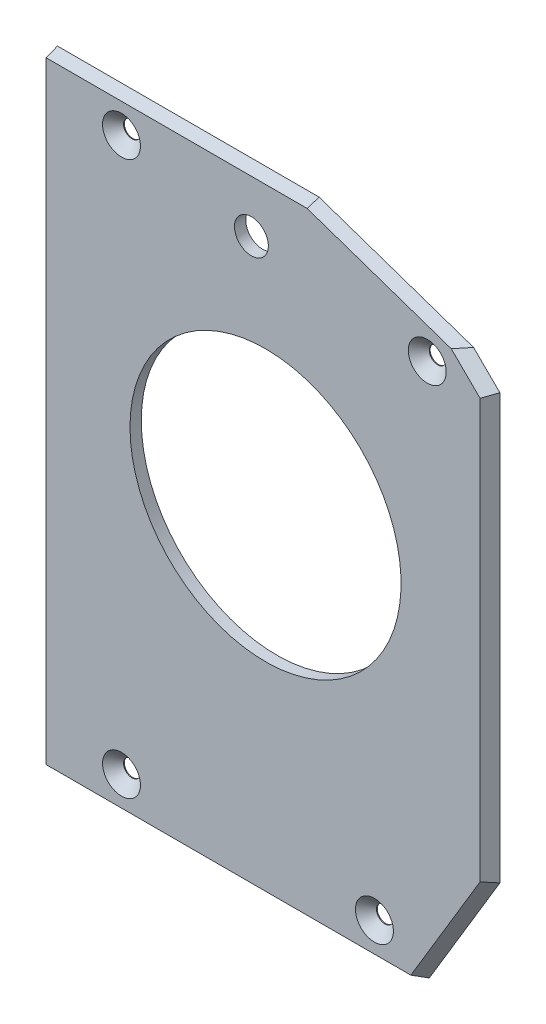
SolidWorks part; units mm, degrees
ref_plane "Front Plane" through (0, 0, 0) normal (0, 0, 1) x (1, 0, 0)
ref_plane "Top Plane" through (0, 0, 0) normal (0, 1, 0) x (1, 0, 0)
ref_plane "Right Plane" through (0, 0, 0) normal (1, 0, 0) x (0, 0, -1)
sketch "Sketch1" plane through (0, 0, 0) normal (0, 0, 1) x (1, 0, 0)
  line L9 (38.85, -60) -> (38.85, 50)
  line L12 (-39.5, 36.014) -> (-39.5, -39.169)
  line L13 (38.85, 50) -> (-7.5, 50)
  line L14 (-7.5, 50) -> (-34.8474, 40.6238)
  line L16 (-39.5, -39.169) -> (-27.0014, -60)
  line L17 (-27.0014, -60) -> (38.85, -60)
  line L171 (-34.8474, 40.6238) -> (-39.5, 36.014)
  circle A2 centre (0, 0) radius 23
  circle A3 centre (0, 0) radius 24
extrude "Boss-Extrude1" add sketch "Sketch1" along normal blind 2 contours L16 L17 L9 L13 L14 L12 A3 region at (5.9243, -58.6495, 0)
chamfer "Chamfer1" distance 2 distance2 1.5 3 edges at (-39.5, -1.5775, 2) (-33.2507, -49.5845, 2) (-37.1737, 38.3189, 2) first distance on face at (-39.5, -1.5775, 1) first distance on face at (-33.2507, -49.5845, 1) first distance on face at (-37.1737, 38.3189, 1)
sketch "Sketch3" plane through (0, 0, 2) normal (0, 0, 1) x (1, 0, 0)
  line L0 (-42.5, -40) -> (-42.5, 33.1739) construction
  line L4 (-7.5, 50) -> (38.85, 50) construction
  circle A0 centre (2.5, 40) radius 3
  circle A1 centre (-19.2911, -54) radius 1.5 construction
  circle A2 centre (25.5, -54) radius 1.5 construction
  circle A3 centre (25.5, 44) radius 1.5 construction
  circle A4 centre (-28.6429, 36.4081) radius 1.5 construction
  circle A5 centre (-19.2911, -54) radius 1.5
  circle A6 centre (25.5, -54) radius 1.5
  circle A7 centre (25.5, 44) radius 1.5
  circle A8 centre (-28.6429, 36.4081) radius 1.5
  dimension "D1" = 45
  dimension "D3" = 6
  dimension "D2" = 10
extrude "Cut-Extrude1" cut sketch "Sketch3" against normal blind 2
chamfer "Chamfer2" distance 2 distance2 0.8 3 edges at (6.7989, -60, 2) (15.675, 50, 2) (-19.5442, 45.8706, 2) first distance on face at (6.3616, -60, 1) first distance on face at (15.675, 50, 1) first distance on face at (-20.3589, 45.5912, 1)
chamfer "Chamfer3" distance 1.86 angle 45 4 edges at (-17.7911, -54, 2) (27, -54, 2) (27, 44, 2) (-27.1429, 36.4081, 2)
ref_plane "Plane1" through (48.85, 0, 0) normal (1, 0, 0) x (0, 0, -1)
mirror "Mirror1" about plane through (48.85, 0, 0) normal (1, 0, 0) of bodies 102
delete or keep bodies "Body-Delete/Keep 1" type delete bodies bodies 102
